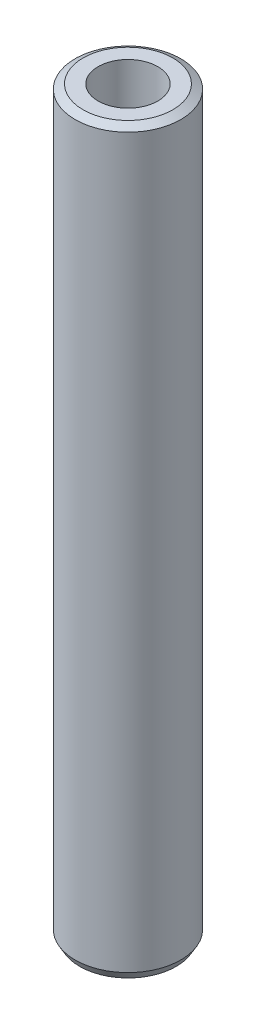
SolidWorks part; units mm, degrees
ref_plane "Front Plane" through (0, 0, 0) normal (0, 0, 1) x (1, 0, 0)
ref_plane "Top Plane" through (0, 0, 0) normal (0, 1, 0) x (1, 0, 0)
ref_plane "Right Plane" through (0, 0, 0) normal (1, 0, 0) x (0, 0, -1)
sketch "Sketch1" plane through (0, 0, 0) normal (0, 1, 0) x (1, 0, 0)
  circle A0 centre (0, 0) radius 37.5
  dimension "SHAFT_OD" = 75
extrude "Boss-Extrude1" add sketch "Sketch1" along normal blind 525.6989
sketch "Sketch2" plane through (0, 0, 0) normal (0, 1, 0) x (1, 0, 0)
  circle A0 centre (0, 0) radius 21.1974
  dimension "BORE_D" = 42.3949
extrude "Cut-Extrude1" cut sketch "Sketch2" along normal through all
chamfer "Chamfer1" distance 3.2426 angle 60 2 edges at (0, 525.6989, 37.5) (0, 0, 37.5) first distance on face at (0, 525.6989, 37.5) first distance on face at (0, 0, 21.1974)
